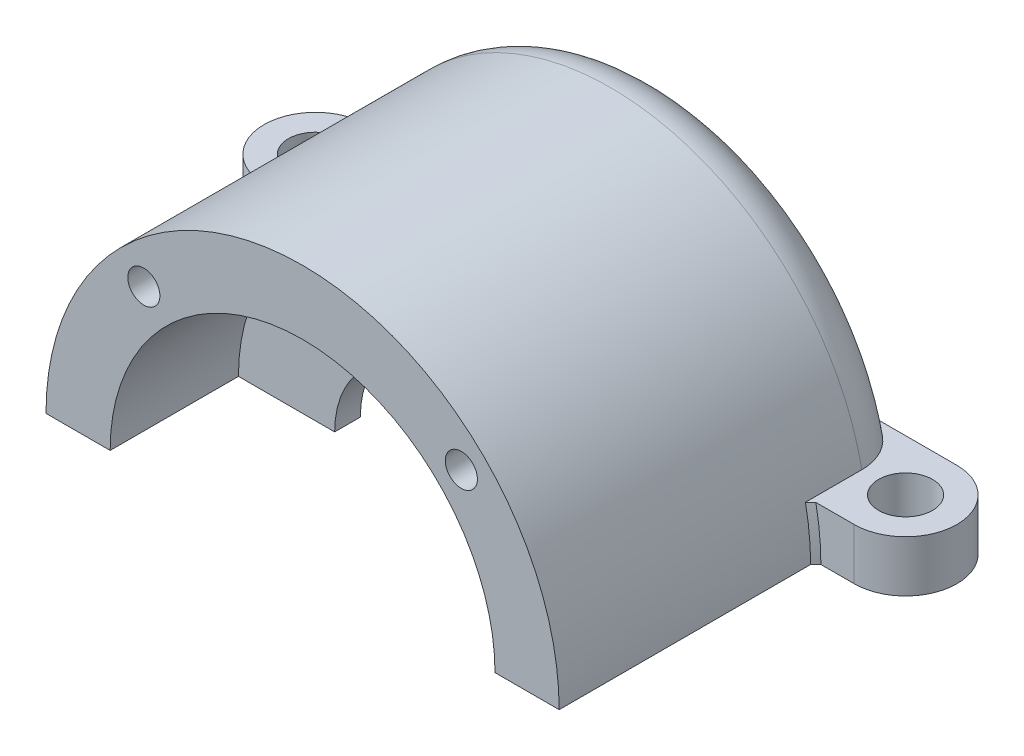
SolidWorks part; units mm, degrees
material "Литая углеродистая сталь"
ref_plane "Спереди" through (0, 0, 0) normal (0, 0, 1) x (1, 0, 0)
ref_plane "Сверху" through (0, 0, 0) normal (0, 1, 0) x (1, 0, 0)
ref_plane "Справа" through (0, 0, 0) normal (1, 0, 0) x (0, 0, -1)
sketch "Эскиз1" plane through (0, 0, 0) normal (0, 1, 0) x (1, 0, 0)
  line L0 (-15, 0) -> (-15, 10)
  line L1 (-15, 10) -> (-7.5, 10)
  line L4 (-20, 28) -> (-20, 0)
  line L5 (-20, 0) -> (-15, 0)
  line L7 (-20, 28) -> (-11, 28)
  line L9 (-11, 28) -> (-11, 12)
  line L10 (0, 0) -> (0, 50000) construction
  line L12 (-7.5, 10) -> (-7.5, 12)
  line L13 (-7.5, 12) -> (-11, 12)
  dimension "D1" = 15
  dimension "D2" = 20
  dimension "D3" = 10
  dimension "D4" = 7.5
  dimension "D5" = 28
  dimension "D6" = 2
  dimension "D7" = 11
revolve "Повернуть1" add sketch "Эскиз1" angle 180 about L10
sketch "Эскиз2" plane through (0, 0, 0) normal (0, 1, 0) x (1, 0, 0)
  line L5 (11, 28) -> (23, 28)
  line L6 (11, 28) -> (11, 20)
  line L7 (11, 12) -> (11, 28) construction
  line L8 (11, 20) -> (23, 20)
  arc A1 (23, 28) -> (23, 20) centre (23, 24) cw
  dimension "D1" = 12
extrude "Бобышка-Вытянуть1" add sketch "Эскиз2" along normal blind 4
sketch "Эскиз3" plane through (0, 4, 0) normal (0, 1, 0) x (1, 0, 0)
  circle A0 centre (23, 24) radius 2.1
  arc A1 (23, 20) -> (23, 28) centre (23, 24) ccw construction
  dimension "D1" = 4.2
extrude "Вырез-Вытянуть1" cut sketch "Эскиз3" against normal up to next
mirror "Зеркальное отражение1" about plane through (0, 0, 0) normal (1, 0, 0) of "Вырез-Вытянуть1", "Бобышка-Вытянуть1"
sketch "Эскиз4" plane through (0, 0, -10) normal (0, 0, 1) x (1, 0, 0)
  line L0 (0, 0) -> (15, 0) construction
  circle A0 centre (4.75, 8.2272) radius 1.1
  dimension "D2" = 2.2
  dimension "D1" = 9.5
  dimension "D3" = 60
extrude "Вырез-Вытянуть2" cut sketch "Эскиз4" against normal up to next
pattern_circular "Круговой массив1" count 2 every 60 about axis through (0, 0, 0) along (0, 0, 1) of "Вырез-Вытянуть2"
hole_wizard "Сверление под метчик M31" positions "Трехмерный эскиз1" profile "Эскиз5" hole size "M3" standard "ISO"
sketch3d "Трехмерный эскиз1"
  line L0 (0, 0, 0) -> (20, 0, 0) construction
  point P0 (12.3744, 12.3744, 0)
  dimension "D1" = 17.5
  dimension "D2" = 45
sketch "Эскиз5" plane through (12.3744, 12.3744, 0) normal (1, 0, 0) x (0, -1, 0)
  line L0 (0, 0) -> (0, 15.7511)
  line L1 (0, 15.7511) -> (1.25, 15)
  line L2 (1.25, 15) -> (1.25, 0)
  line L5 (1.25, 0) -> (0, 0)
  line L10 (0, 15.7511) -> (-1.25, 15) construction
  line L11 (0, -6.35) -> (0, 107.95) construction
  dimension "Диаметр отверстия" = 2.5
  dimension "Глубина отверстия" = 15
  dimension "Угол заточки сверла" = 118
cosmetic thread "Условное изображение резьбы1" parameters "D2"=3
pattern_circular "Круговой массив2" count 2 every 90 about axis through (0, 0, 0) along (0, 0, 1) of "Сверление под метчик M31"
chamfer "Фаска1" distance 0.4 angle 45 2 edges at (-19.8987, 2.0102, -20) (19.8987, 2.0102, -20)
fillet "Скругление1" radius 4 1 edges at (0, 20, -28)
